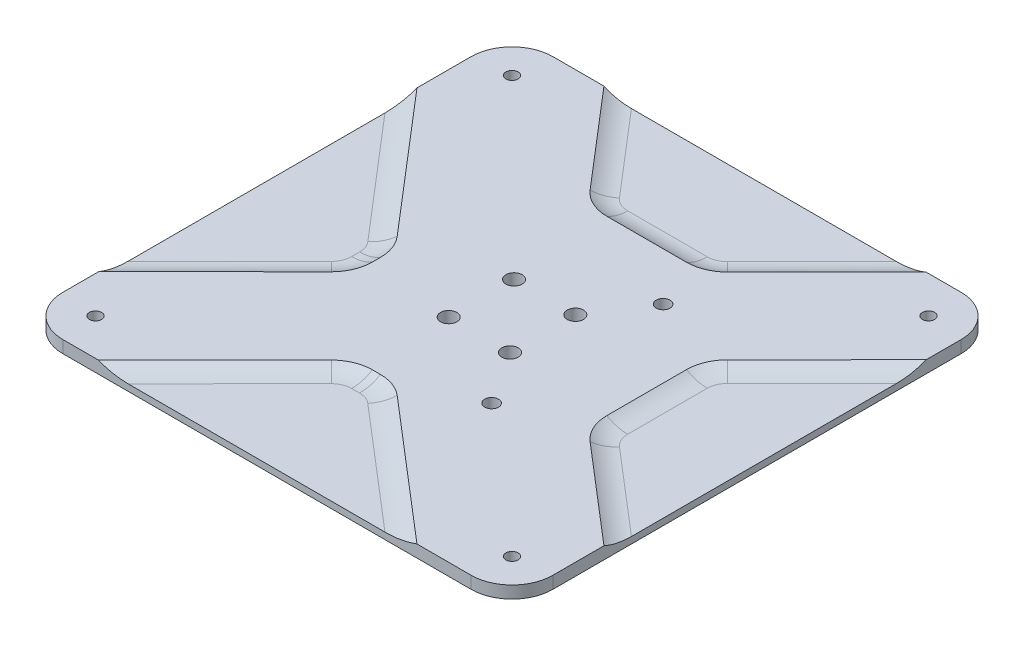
SolidWorks part; units mm, degrees
material "ABS"
ref_plane "Alzado" through (0, 0, 0) normal (0, 0, 1) x (1, 0, 0)
ref_plane "Planta" through (0, 0, 0) normal (0, 1, 0) x (1, 0, 0)
ref_plane "Vista lateral" through (0, 0, 0) normal (1, 0, 0) x (0, 0, -1)
sketch "Sketch1" plane through (0, 0, 0) normal (0, 1, 0) x (1, 0, 0)
  line L1 (-7.5, -8) -> (7.5, -8) construction
  line L2 (-7.5, -8) -> (-7.5, 8) construction
  line L3 (-7.5, 8) -> (7.5, 8) construction
  line L4 (7.5, -8) -> (7.5, 8) construction
  line L5 (-7.5, -8) -> (7.5, 8) construction
  line L6 (-7.5, 8) -> (7.5, -8) construction
  line L7 (-60, -60) -> (60, -60)
  line L8 (-60, -60) -> (-60, 60)
  line L9 (-60, 60) -> (60, 60)
  line L10 (60, -60) -> (60, 60)
  circle A0 centre (-7.5, -8) radius 2
  circle A1 centre (7.5, 8) radius 2
  circle A2 centre (7.5, -8) radius 2
  circle A3 centre (-7.5, 8) radius 2
  point P0 (0, 0)
  point P10 (0, 0)
  point P16 (-60, 0)
  point P17 (0, -60)
  dimension "D3" = 4
  dimension "D1" = 16
  dimension "D2" = 15
  dimension "D4" = 120
  dimension "D5" = 120
extrude "Boss-Extrude1" add sketch "Sketch1" along normal blind 3
fillet "Fillet1" radius 10 4 edges at (-60, 1.5, -60) (60, 1.5, -60) (60, 1.5, 60) (-60, 1.5, 60)
sketch "Sketch2" plane through (0, 3, 0) normal (0, 1, 0) x (1, 0, 0)
  line L0 (50, 60) -> (-50, 60) construction
  line L1 (-60, 50) -> (-60, -50) construction
  circle A0 centre (-51, 51) radius 1.5
  point P2 (-55, 55)
  dimension "D1" = 3
  dimension "D2" = 9
  dimension "D3" = 9
extrude "Cut-Extrude1" cut sketch "Sketch2" against normal through all
mirror "Mirror3" about plane through (0, 0, 0) normal (0, 0, 1) of "Cut-Extrude1" second plane through (0, 0, 0) second plane normal (1, 0, 0)
sketch "Sketch3" plane through (0, 3, 0) normal (0, 1, 0) x (1, 0, 0)
  line L0 (16, 21) -> (16, -21) construction
  circle A2 centre (16, 21) radius 1.7
  circle A3 centre (16, -21) radius 1.7
  point P4 (16, 0)
  dimension "D2" = 42
  dimension "D1" = 3.4
  dimension "D3" = 16
extrude "Cut-Extrude2" cut sketch "Sketch3" against normal through all
sketch "Sketch5" plane through (0, 3, 0) normal (0, 1, 0) x (1, 0, 0)
  line L0 (60, 41.4316) -> (32.7473, 14.122)
  line L1 (60, -50) -> (60, 50) construction
  line L2 (32.7473, 14.122) -> (32.7473, -14.122)
  line L3 (32.7473, -14.122) -> (60, -37.4814)
  line L4 (0, 60) -> (0, -60) construction
  line L5 (60, 41.4316) -> (60, -37.4814)
  line L6 (-50, -60) -> (50, -60) construction
  line L7 (36.7283, -60) -> (0, -28.5186)
  line L8 (0, -28.5186) -> (-9.8043, -28.5186)
  line L9 (-9.8043, -28.5186) -> (-41.22, -60)
  line L10 (-60, 0) -> (60, 0) construction
  line L11 (-41.22, -60) -> (36.7283, -60)
  line L12 (16, -21) -> (51, -51) construction
  line L13 (16, 21) -> (16, -21) construction
  line L14 (0, -28.5186) -> (9.8043, -28.5186) construction
  line L15 (9.8043, -28.5186) -> (9.8043, -36.9222) construction
  line L16 (60, -37.4814) -> (36.7283, -60) construction
  line L17 (57.0711, 57.0711) -> (-58.3189, -58.3189) construction
  line L18 (-60, -41.22) -> (-60, 36.7283)
  line L19 (-28.5186, -9.8043) -> (-60, -41.22)
  line L20 (-28.5186, 0) -> (-28.5186, -9.8043)
  line L21 (-60, 36.7283) -> (-28.5186, 0)
  line L22 (41.4316, 60) -> (-37.4814, 60)
  line L23 (-14.122, 32.7473) -> (-37.4814, 60)
  line L24 (14.122, 32.7473) -> (-14.122, 32.7473)
  line L25 (41.4316, 60) -> (14.122, 32.7473)
  arc A0 (60, 50) -> (50, 60) centre (50, 50) ccw construction
  point P18 (48.3642, -48.7407)
  point P20 (32.7473, 0)
  point P22 (-11.1597, -28.7679)
extrude "Cut-Extrude3" cut sketch "Sketch5" against normal blind 1.4
fillet "Fillet2" radius 10 8 edges at (-28.5186, 2.3, 9.8043) (-28.5186, 2.3, 0) (-14.122, 2.3, -32.7473) (14.122, 2.3, -32.7473) (32.7473, 2.3, 14.122) (32.7473, 2.3, -14.122) (0, 2.3, 28.5186) (-9.8043, 2.3, 28.5186)
fillet "Fillet3" radius 10 20 edges at (-45.7274, 1.6, 26.9773) (-29.2818, 1.6, 9.4877) (-28.5186, 1.6, 4.6776) (-45.463, 1.6, -19.7685) (19.7685, 1.6, 45.463) (-0.2298, 1.6, 29.1397) (-4.6776, 1.6, 28.5186) (-26.9773, 1.6, 45.7274) (-27.2983, 1.6, -48.1197) (-13.7012, 1.6, -33.6622) (29.2407, 1.6, -47.8344) (13.808, 1.6, -33.5065) (48.1197, 1.6, 27.2983) (33.6622, 1.6, 13.7012) (32.7473, 1.6, -0.2317) (33.5065, 1.6, -13.808) (-29.1397, 1.6, 0.2298) (-9.4877, 1.6, 29.2818) (0.2317, 1.6, -32.7473) (47.8344, 1.6, -29.2407)
